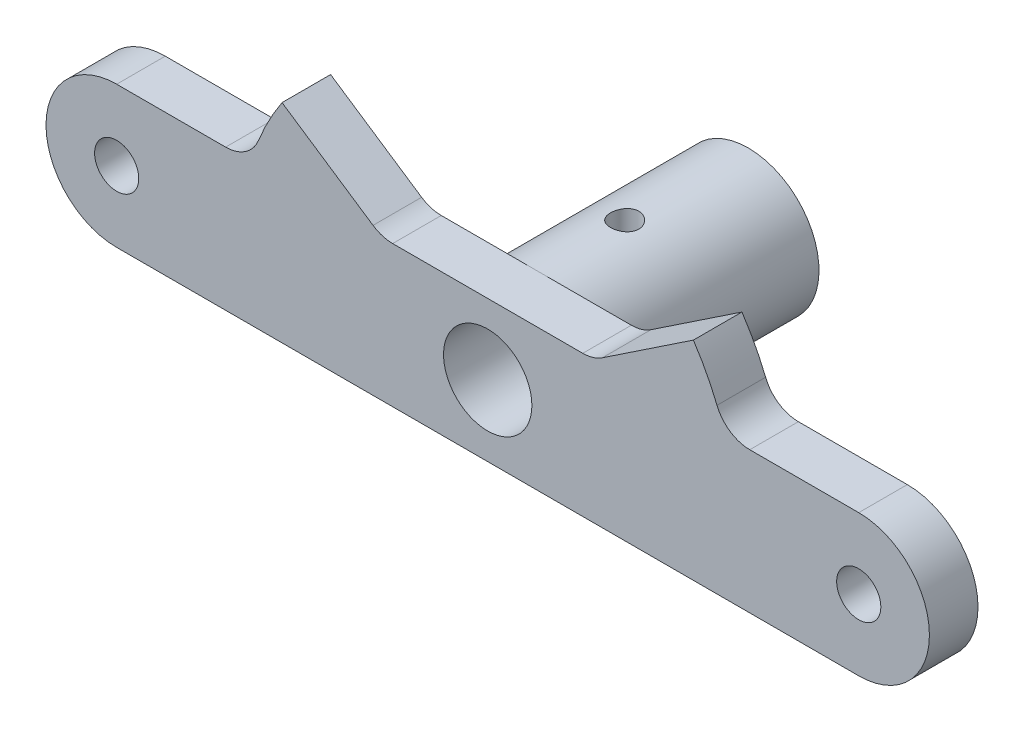
SolidWorks part; units mm, degrees
material "3.1355 (EN-AW 2024)"
ref_plane "Спереди" through (0, 0, 0) normal (0, 0, 1) x (1, 0, 0)
ref_plane "Сверху" through (0, 0, 0) normal (0, 1, 0) x (1, 0, 0)
ref_plane "Справа" through (0, 0, 0) normal (1, 0, 0) x (0, 0, -1)
sketch "Эскиз1" plane through (0, 0, 0) normal (0, 0, 1) x (1, 0, 0)
  line L0 (-25, 4) -> (25, 4)
  line L2 (-25, 4) -> (-25, -4)
  line L4 (25, 4) -> (25, -4)
  line L10 (0, 0) -> (0, 4) construction
  line L11 (0, 0) -> (0, -4) construction
  line L12 (-25, -4) -> (25, -4)
  point P0 (0, 0)
  dimension "D2" = 8
  dimension "D1" = 50
extrude "База" add sketch "Эскиз1" along normal blind 2.75
sketch "Эскиз6" plane through (0, 0, 0) normal (0, 0, -1) x (-1, 0, 0)
  circle A0 centre (0, 0) radius 4
  dimension "D1" = 8
extrude "Посадка на вал" add sketch "Эскиз6" along normal blind 12
hole_wizard "Крепление толкателей M3" positions "Эскиз4" profile "Эскиз5" tap size "M3" standard "DIN" end condition through all
sketch "Эскиз4" plane through (0, 0, 2.75) normal (0, 0, 1) x (1, 0, 0)
  line L8 (-21, 0) -> (-25, 0) construction
  line L12 (21, 0) -> (25, 0) construction
  line L14 (25, -4) -> (25, 4) construction
  line L15 (-25, 4) -> (-25, -4) construction
  point P0 (-21, 0)
  point P2 (21, 0)
  dimension "D1" = 4
sketch "Эскиз5" plane through (-21, 0, 2.75) normal (1, 0, 0) x (0, -1, 0)
  line L0 (0, 0) -> (0, 14.75)
  line L1 (0, 14.75) -> (1.25, 14.75)
  line L2 (1.25, 14.75) -> (1.25, 0)
  line L5 (1.25, 0) -> (0, 0)
  line L11 (0, -6.35) -> (0, 107.95) construction
  dimension "Диаметр проходного сверла" = 2.5
  dimension "Глубина проходного сверла" = 14.75
cosmetic thread "Отверстие резьбы3" parameters "D2"=3
cosmetic thread "Отверстие резьбы4" parameters "D2"=3
hole_wizard "Крепление вала M2" positions "Трехмерный эскиз1" profile "Эскиз7" tap size "M2" standard "DIN" end condition through all
sketch3d "Трехмерный эскиз1"
  point P0 (0, 4, -5)
  dimension "D1" = 5
sketch "Эскиз7" plane through (0, 4, -5) normal (1, 0, 0) x (0, 0, 1)
  line L0 (0, 0) -> (0, 8)
  line L1 (0, 8) -> (0.8, 8)
  line L2 (0.8, 8) -> (0.8, 0)
  line L5 (0.8, 0) -> (0, 0)
  line L11 (0, -6.35) -> (0, 107.95) construction
  dimension "Диаметр проходного сверла" = 1.6
  dimension "Глубина проходного сверла" = 8
cosmetic thread "Отверстие резьбы5" parameters "D2"=2
sketch "Эскиз11" plane through (0, 0, 2.75) normal (0, 0, 1) x (1, 0, 0)
  line L0 (-14, 0) -> (0, 0)
  line L1 (0, 0) -> (14, 0)
  arc A0 (-14, 0) -> (14, 0) centre (0, 0) cw
  dimension "D1" = 14
extrude "ПерекрытиеДатчика" add sketch "Эскиз11" against normal up to surface (2.75 mm away) up to face at (19.75, 0, 0)
sketch "Эскиз12" plane through (0, 0, 2.75) normal (0, 0, 1) x (1, 0, 0)
  line L0 (-5.9864, 4) -> (5.9864, 4)
  line L1 (-13.4164, 4) -> (-25, 4) construction
  line L3 (5.9864, 4) -> (11.6406, 7.778)
  line L4 (-5.9864, 4) -> (-11.6406, 7.778)
  arc A0 (13.4164, 4) -> (-13.4164, 4) centre (0, 0) ccw construction
  arc A1 (-11.6406, 7.778) -> (11.6406, 7.778) centre (0, 0) cw
  point P5 (0, 4)
  dimension "D1" = 112.5
extrude "ВырезДатчика" cut sketch "Эскиз12" against normal up to surface (2.75 mm away) up to face at (-0.5, 1.75, 0)
sketch "Эскиз10" plane through (0, 0, -12) normal (0, 0, 1) x (1, 0, 0)
  circle A0 centre (0, 0) radius 2.5
  dimension "D1" = 5
extrude "Вырез на вал" cut sketch "Эскиз10" along normal through all
fillet "Скругление4" 2 edges at (-25, 4, 1.375) (-25, -4, 1.375) type full round first side face at (-19.2082, 4, 1.375) second side face at (0, -4, 1.1) middle face at (-25, 0, 1.375)
fillet "Скругление5" 2 edges at (25, 4, 1.375) (25, -4, 1.375) type full round first side face at (19.2082, 4, 1.375) second side face at (1.6, -4, 1.1) middle face at (25, 0, 1.375)
fillet "Скругление6" radius 2 4 edges at (13.4164, 4, 1.375) (5.9864, 4, 1.375) (-5.9864, 4, 1.375) (-13.4164, 4, 1.375)
